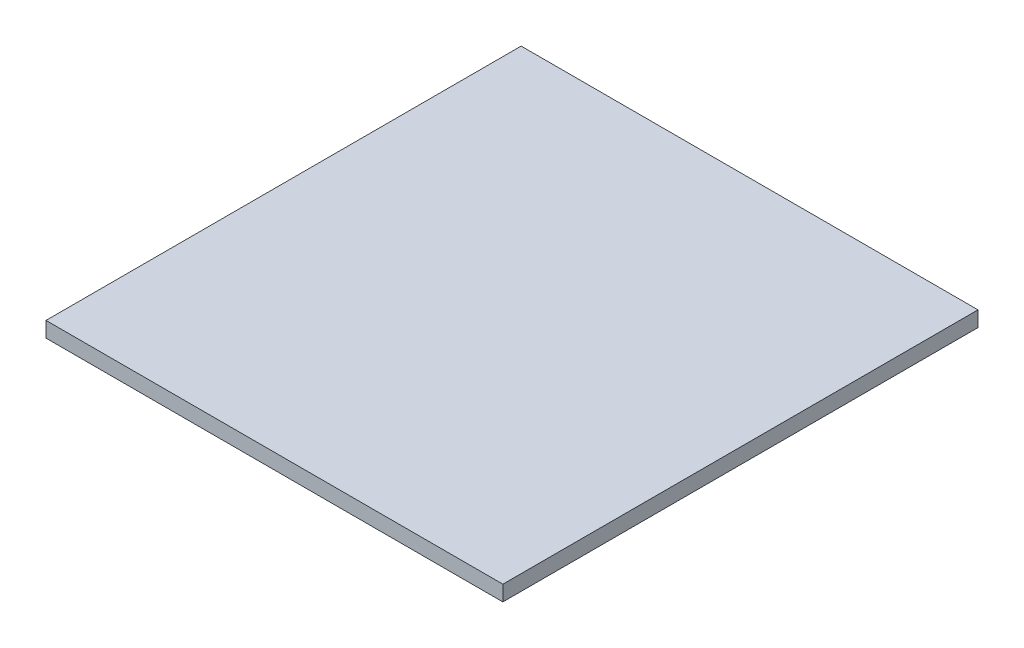
SolidWorks part; units mm, degrees
ref_plane "Front Plane" through (0, 0, 0) normal (0, 0, 1) x (1, 0, 0)
ref_plane "Top Plane" through (0, 0, 0) normal (0, 1, 0) x (1, 0, 0)
ref_plane "Right Plane" through (0, 0, 0) normal (1, 0, 0) x (0, 0, -1)
sketch "Sketch1" plane through (0, 0, 0) normal (0, 1, 0) x (1, 0, 0)
  line L1 (-44.2815, 20.698) -> (50.7185, 20.698)
  line L2 (-44.2815, 20.698) -> (-44.2815, -78.102)
  line L3 (-44.2815, -78.102) -> (50.7185, -78.102)
  line L4 (50.7185, 20.698) -> (50.7185, -78.102)
  dimension "D1" = 95
  dimension "D2" = 98.8
extrude "Boss-Extrude1" add sketch "Sketch1" along normal blind 3.2
equation "\"Fit\"= 1"
equation "\"cover width\"= 98.8"
equation "\"top 1 length\" = 95"
equation "\"thinner acrylic\" = 3.2"
equation "\"D1@Sketch1\"=\"top 1 length\""
equation "\"D2@Sketch1\"=\"cover width\""
equation "\"D1@Boss-Extrude1\"=\"thinner acrylic\""
